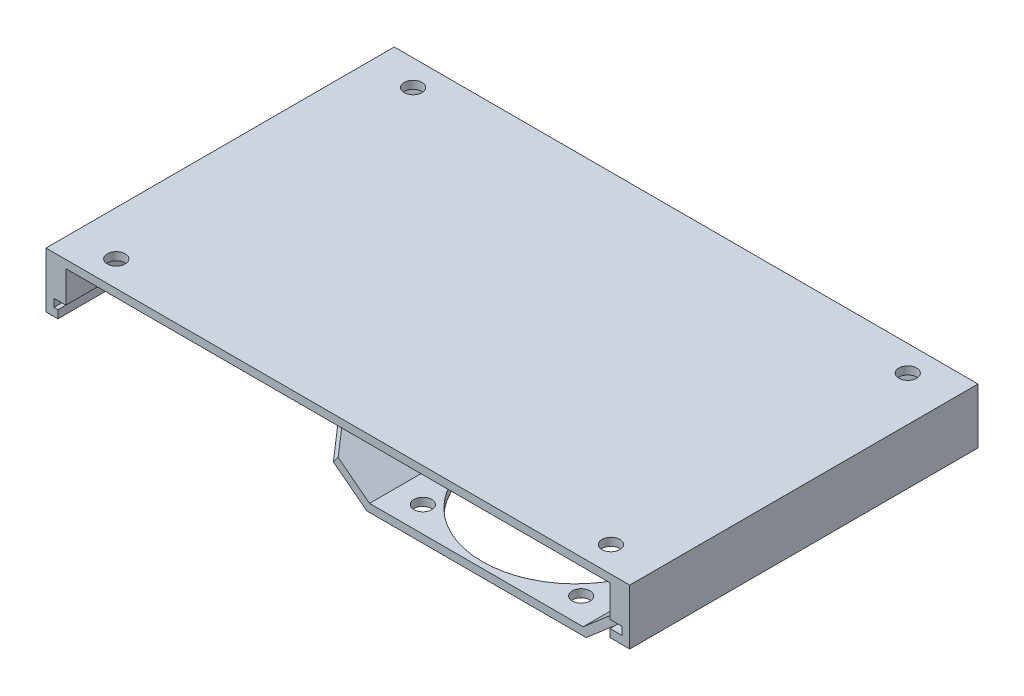
SolidWorks part; units mm, degrees
ref_plane "Front Plane" through (0, 0, 0) normal (0, 0, 1) x (1, 0, 0)
ref_plane "Top Plane" through (0, 0, 0) normal (0, 1, 0) x (1, 0, 0)
ref_plane "Right Plane" through (0, 0, 0) normal (1, 0, 0) x (0, 0, -1)
sketch "Sketch1" plane through (0, 0, 0) normal (0, 0, 1) x (1, 0, 0)
  line L0 (0, 0) -> (68.75, 0)
  line L1 (68.75, 0) -> (68.75, -8)
  line L2 (68.75, -8) -> (71.75, -8)
  line L3 (71.75, -8) -> (71.75, -10)
  line L4 (71.75, -10) -> (68.75, -10)
  line L5 (0, 0) -> (-68.75, 0)
  line L6 (-68.75, 0) -> (-68.75, -8)
  line L7 (-68.75, -8) -> (-71.75, -8)
  line L8 (-71.75, -8) -> (-71.75, -10)
  line L9 (-71.75, -10) -> (-70.75, -10)
  line L10 (73.75, -12) -> (68.75, -12)
  line L11 (73.75, -6) -> (73.75, -12)
  line L14 (0, 2) -> (70.75, 2)
  line L15 (0, 2) -> (-70.75, 2)
  line L18 (-73.75, -6) -> (-73.75, -12)
  line L19 (-73.75, -12) -> (-70.75, -12)
  line L20 (-70.75, -10) -> (-70.75, -12)
  line L21 (68.75, -10) -> (68.75, -12)
  line L22 (-73.75, -6) -> (-73.75, 2)
  line L23 (-73.75, 2) -> (-70.75, 2)
  line L24 (70.75, 2) -> (73.75, 2)
  line L25 (73.75, 2) -> (73.75, -6)
  line L27 (70.75, 2) -> (70.75, -6) construction
  line L28 (70.75, -6) -> (73.75, -6) construction
  line L29 (-70.75, 2) -> (-70.75, -6) construction
  line L30 (-70.75, -6) -> (-73.75, -6) construction
  dimension "D1" = 143.5
  dimension "D2" = 1
  dimension "D3" = 2
  dimension "D4" = 3
  dimension "D5" = 8
  dimension "D6" = 2
extrude "Boss-Extrude1" add sketch "Sketch1" along normal blind 85
sketch "Sketch2" plane through (0, 0, 0) normal (0, 0, -1) x (-1, 0, 0)
  line L0 (27, -48) -> (-27, -48)
  line L11 (73.75, -12) -> (27, -48)
  line L12 (-27, -48) -> (-68.75, -12)
  line L27 (-68.75, 0) -> (68.75, 0)
  line L28 (68.75, 0) -> (68.75, -8)
  line L29 (68.75, -8) -> (71.75, -8)
  line L30 (71.75, -8) -> (71.75, -10)
  line L31 (71.75, -10) -> (70.75, -10)
  line L32 (70.75, -10) -> (70.75, -12)
  line L33 (70.75, -12) -> (73.75, -12)
  line L34 (73.75, -12) -> (73.75, 2)
  line L35 (73.75, 2) -> (-73.75, 2)
  line L36 (-73.75, 2) -> (-73.75, -12)
  line L37 (-73.75, -12) -> (-68.75, -12)
  line L38 (-68.75, -12) -> (-68.75, -10)
  line L39 (-68.75, -10) -> (-71.75, -10)
  line L40 (-71.75, -10) -> (-71.75, -8)
  line L41 (-71.75, -8) -> (-68.75, -8)
  line L42 (-68.75, -8) -> (-68.75, 0)
  line L50 (73.75, -12) -> (73.75, 2)
  line L51 (73.75, 2) -> (-73.75, 2)
  line L52 (-73.75, 2) -> (-73.75, -12)
  line L53 (-73.75, -12) -> (-68.75, -12)
  point P3 (-25, -50)
  point P5 (25, -50)
  line M21 (-68.75, 0) -> (68.75, 0)
  line M22 (68.75, 0) -> (68.75, -8)
  line M23 (68.75, -8) -> (71.75, -8)
  line M24 (71.75, -8) -> (71.75, -10)
  line M25 (71.75, -10) -> (70.75, -10)
  line M26 (70.75, -10) -> (70.75, -12)
  line M27 (70.75, -12) -> (73.75, -12)
  line M28 (73.75, -12) -> (73.75, 2)
  line M29 (73.75, 2) -> (-73.75, 2)
  line M30 (-73.75, 2) -> (-73.75, -12)
  line M31 (-73.75, -12) -> (-68.75, -12)
  line M32 (-68.75, -12) -> (-68.75, -10)
  line M33 (-68.75, -10) -> (-71.75, -10)
  line M34 (-71.75, -10) -> (-71.75, -8)
  line M35 (-71.75, -8) -> (-68.75, -8)
  line M36 (-68.75, -8) -> (-68.75, 0)
  dimension "D5" = 0
extrude "Boss-Extrude2" add sketch "Sketch2" along normal blind 3 contours L12 L11 | M36 M21 M22 M23 M24 M25 M26 M27 M28 M29 M30 M31 M32 M33 M34 M35 region at (-1.0309, -20.4889, 0) region at (-72.25, -10.5184, 0)
sketch "Sketch4" plane through (0, 0, -3) normal (0, 0, -1) x (-1, 0, 0)
  line L0 (42.8462, -35.7976) -> (27, -48)
  line L1 (73.75, -12) -> (27, -48) construction
  line L2 (27, -48) -> (-27, -48)
  line L3 (-27, -48) -> (-42.1467, -34.9394)
  line L4 (-27, -48) -> (-68.75, -12) construction
  dimension "D1" = 20
extrude "Extrude-Thin1" add sketch "Sketch4" against normal blind 53 thin thin type one direction reverse wall 2
chamfer "Chamfer1" distance 10 angle 45 2 edges at (42.7997, -35.6967, 50) (-43.4563, -36.5899, 50)
chamfer "Chamfer2" distance 2 angle 45 2 edges at (-42.8462, -35.7976, -1.5) (42.1467, -34.9394, -1.5)
sketch "Sketch5" plane through (0, 0, 0) normal (0, 0, 1) x (1, 0, 0)
  line L0 (-30, -31.267) -> (30, -31.267) construction
  line L1 (-30, -28.267) -> (30, -28.267)
  line L2 (-30, -34.267) -> (30, -34.267)
  line L3 (-68.75, 0) -> (68.75, 0) construction
  line L4 (0, 0) -> (0, -31.267) construction
  arc A0 (-30, -28.267) -> (-30, -34.267) centre (-30, -31.267) ccw
  arc A1 (30, -34.267) -> (30, -28.267) centre (30, -31.267) ccw
  point P2 (0, -31.267)
  dimension "D1" = 3
  dimension "D2" = 60
extrude "Cut-Extrude1" cut sketch "Sketch5" against normal blind 53
sketch "Sketch6" plane through (0, -48, 0) normal (0, 1, 0) x (1, 0, 0)
  line L0 (27, -50) -> (-27, 0) construction
  line L1 (-27, -50) -> (27, 0) construction
  line L2 (20, -43.5185) -> (-20, -43.5185) construction
  line L3 (-20, -43.5185) -> (-20, -6.4815) construction
  line L4 (-20, -6.4815) -> (20, -6.4815) construction
  line L5 (20, -6.4815) -> (20, -43.5185) construction
  line L6 (-27, 0) -> (27, 0) construction
  line L7 (27, -50) -> (27, 0) construction
  circle A0 centre (0, -25) radius 23.5
  circle A1 centre (20, -43.5185) radius 2.25
  circle A2 centre (-20, -43.5185) radius 2.25
  circle A3 centre (-20, -6.4815) radius 2.25
  circle A4 centre (20, -6.4815) radius 2.25
  dimension "D1" = 47
  dimension "D2" = 4.5
  dimension "D3" = 40
extrude "Cut-Extrude2" cut sketch "Sketch6" against normal blind 53
sketch "Sketch7" plane through (0, 2, 0) normal (0, 1, 0) x (1, 0, 0)
  line L0 (73.75, -78.5) -> (-73.75, -78.5) construction
  line L1 (73.75, -85) -> (73.75, 3) construction
  line L2 (-73.75, -85) -> (-73.75, 3) construction
  line L3 (73.75, -3.5) -> (-73.75, -3.5) construction
  line L4 (0, -78.5) -> (0, -59.4669) construction
  line L5 (0, -78.5) -> (0, -85) construction
  line L6 (73.75, -85) -> (-73.75, -85) construction
  line L7 (0, -3.5) -> (0, 3) construction
  line L8 (-73.75, 3) -> (73.75, 3) construction
  circle A0 centre (62.5, -78.5) radius 2.25
  circle A1 centre (62.5, -3.5) radius 2.25
  circle A2 centre (-62.5, -3.5) radius 2.25
  circle A3 centre (-62.5, -78.5) radius 2.25
  dimension "D2" = 62.5
  dimension "D4" = 4.5
  dimension "D1" = 75
  dimension "D3" = 62.5
extrude "Cut-Extrude3" cut sketch "Sketch7" against normal blind 53
